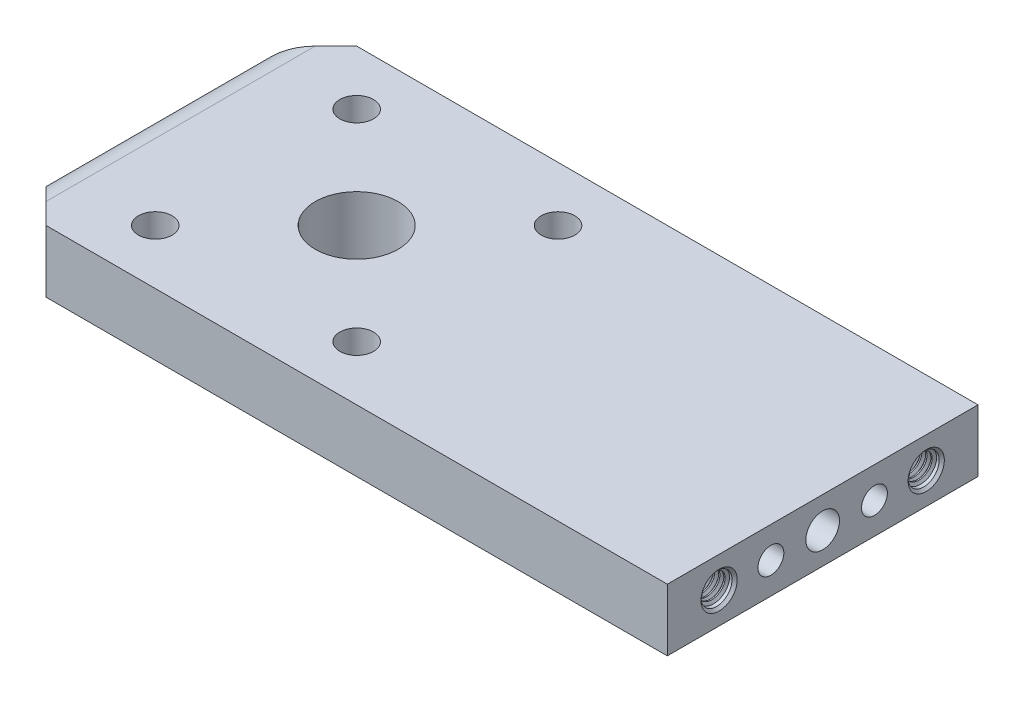
SolidWorks part; units mm, degrees
ref_plane "Front Plane" through (0, 0, 0) normal (0, 0, 1) x (1, 0, 0)
ref_plane "Top Plane" through (0, 0, 0) normal (0, 1, 0) x (1, 0, 0)
ref_plane "Right Plane" through (0, 0, 0) normal (1, 0, 0) x (0, 0, -1)
sketch "Sketch1" plane through (0, 0, 0) normal (0, 1, 0) x (1, 0, 0)
  line L1 (0, 0) -> (-130, 0)
  line L2 (0, 0) -> (0, 60)
  line L3 (0, 60) -> (-130, 60)
  line L4 (-130, 0) -> (-130, 60)
  dimension "D1" = 130
  dimension "D2" = 60
extrude "Boss-Extrude1" add sketch "Sketch1" along normal blind 12
sketch "Sketch2" plane through (0, 12, 0) normal (0, 1, 0) x (1, 0, 0)
  line L0 (-130, 50) -> (-130, 60)
  line L1 (-130, 60) -> (-130, 0) construction
  line L2 (-130, 60) -> (-120, 60)
  line L3 (0, 60) -> (-130, 60) construction
  line L4 (-130, 0) -> (-130, 10)
  line L5 (-130, 0) -> (-120, 0)
  line L6 (-130, 0) -> (0, 0) construction
  line L7 (-130, 50) -> (-120, 60)
  line L8 (-130, 10) -> (-120, 0)
  dimension "D1" = 10
  dimension "D2" = 10
  dimension "D3" = 10
  dimension "D4" = 10
extrude "Cut-Extrude1" cut sketch "Sketch2" against normal through all
sketch "Sketch3" plane through (0, 12, 0) normal (0, 1, 0) x (1, 0, 0)
  line L0 (0, 0) -> (0, 60) construction
  line L1 (-120, 0) -> (0, 0) construction
  circle A0 centre (-90, 30) radius 8
  dimension "D3" = 16
  dimension "D1" = 90
  dimension "D2" = 30
extrude "Cut-Extrude2" cut sketch "Sketch3" against normal through all
sketch "Sketch4" plane through (0, 12, 0) normal (0, 1, 0) x (1, 0, 0)
  circle A1 centre (-109.4474, 10.5565) radius 3.25
  circle A2 centre (-109.4474, 49.4435) radius 3.25
  circle A3 centre (-70.5526, 49.4435) radius 3.25
  circle A4 centre (-70.5526, 10.5565) radius 3.25
  dimension "D3" = 6.5
  dimension "D4" = 6.5
  dimension "D5" = 6.5
  dimension "D6" = 6.5
extrude "Cut-Extrude3" cut sketch "Sketch4" against normal through all
sketch "Sketch6" plane through (0, 0, -60) normal (0, 0, -1) x (-1, 0, 0)
  line L0 (0, 12) -> (120, 12) construction
  circle A0 centre (95, 6) radius 1.5
  circle A1 centre (85, 6) radius 1.5
  dimension "D3" = 3
  dimension "D4" = 3
  dimension "D2" = 6
  dimension "D5" = 10
extrude "Cut-Extrude4" cut sketch "Sketch6" against normal blind 12
sketch "Sketch7" plane through (0, 0, -60) normal (0, 0, -1) x (-1, 0, 0)
  line L0 (0, 0) -> (120, 0) construction
  circle A0 centre (102, 6) radius 3
  circle A1 centre (78, 6) radius 3
  dimension "D2" = 6
  dimension "D4" = 6
  dimension "D1" = 6
  dimension "D5" = 24
extrude "Cut-Extrude5" cut sketch "Sketch7" against normal blind 20
chamfer "Chamfer1" distance 0.5 angle 45 4 edges at (-81, 6, -60) (-86.5, 6, -60) (-96.5, 6, -60) (-105, 6, -60)
thread "Thread4" pitch 1 method extrude profile "Thread Profile4" start angle 0, offset 0, length 15, pitch 1, diameter 6
ref_plane "Plane4" through (-99, 6, -59.5) normal (0, -1, 0) x (1, 0, 0)
sketch "Thread Profile4" plane through (-99, 6, -59.5) normal (0, -1, 0) x (1, 0, 0)
  line L0 (0, 0) -> (0, 1) construction
  line L11 (0, 0) -> (0, 0.875)
  line L12 (0, 0.875) -> (-0.5413, 0.5625)
  line L13 (-0.5413, 0.5625) -> (-0.5413, 0.3125)
  line L15 (-0.5413, 0.3125) -> (0, 0)
  line L17 (-0.5413, 0.4375) -> (0, 0.4375) construction
  point P2 (0, 0)
  dimension "Pitch" = 1
  dimension "Profile_Angle" = 60
  dimension "Profile_Land" = 0.25
  dimension "Profile_Height" = 0.5413
thread "Thread5" pitch 1 method extrude profile "Thread Profile5" start angle 0, offset 0, length 15, pitch 1, diameter 6
ref_plane "Plane5" through (-75, 6, -59.5) normal (0, -1, 0) x (1, 0, 0)
sketch "Thread Profile5" plane through (-75, 6, -59.5) normal (0, -1, 0) x (1, 0, 0)
  line L0 (0, 0) -> (0, 1) construction
  line L11 (0, 0) -> (0, 0.875)
  line L12 (0, 0.875) -> (-0.5413, 0.5625)
  line L13 (-0.5413, 0.5625) -> (-0.5413, 0.3125)
  line L15 (-0.5413, 0.3125) -> (0, 0)
  line L17 (-0.5413, 0.4375) -> (0, 0.4375) construction
  point P2 (0, 0)
  dimension "Pitch" = 1
  dimension "Profile_Angle" = 60
  dimension "Profile_Land" = 0.25
  dimension "Profile_Height" = 0.5413
fillet "Fillet1" radius 6 4 edges at (-130, 6, -10) (-130, 0, -30) (-130, 6, -50) (-130, 12, -30)
sketch "Sketch20" plane through (0, 0, 0) normal (1, 0, 0) x (0, 0, -1)
  line L0 (0, 0) -> (60, 0) construction
  line L1 (60, 12) -> (60, 0) construction
  circle A0 centre (50, 6) radius 3
  circle A1 centre (10, 6) radius 3
  dimension "D3" = 6
  dimension "D4" = 6
  dimension "D1" = 6
  dimension "D2" = 10
  dimension "D5" = 40
extrude "Cut-Extrude6" cut sketch "Sketch20" against normal blind 20
chamfer "Chamfer2" distance 0.5 angle 45 2 edges at (0, 6, -53) (0, 6, -13)
thread "Thread6" pitch 1 method extrude profile "Thread Profile6" start angle 0, offset 0, length 15, pitch 1, diameter 6
ref_plane "Plane6" through (-0.5, 6, -47) normal (0, -1, 0) x (0, 0, 1)
sketch "Thread Profile6" plane through (-0.5, 6, -47) normal (0, -1, 0) x (0, 0, 1)
  line L0 (0, 0) -> (0, 1) construction
  line L11 (0, 0) -> (0, 0.875)
  line L12 (0, 0.875) -> (-0.5413, 0.5625)
  line L13 (-0.5413, 0.5625) -> (-0.5413, 0.3125)
  line L15 (-0.5413, 0.3125) -> (0, 0)
  line L17 (-0.5413, 0.4375) -> (0, 0.4375) construction
  point P2 (0, 0)
  dimension "Pitch" = 1
  dimension "Profile_Angle" = 60
  dimension "Profile_Land" = 0.25
  dimension "Profile_Height" = 0.5413
thread "Thread7" pitch 1 method extrude profile "Thread Profile7" start angle 0, offset 0, length 15, pitch 1, diameter 6
ref_plane "Plane7" through (-0.5, 6, -7) normal (0, -1, 0) x (0, 0, 1)
sketch "Thread Profile7" plane through (-0.5, 6, -7) normal (0, -1, 0) x (0, 0, 1)
  line L0 (0, 0) -> (0, 1) construction
  line L11 (0, 0) -> (0, 0.875)
  line L12 (0, 0.875) -> (-0.5413, 0.5625)
  line L13 (-0.5413, 0.5625) -> (-0.5413, 0.3125)
  line L15 (-0.5413, 0.3125) -> (0, 0)
  line L17 (-0.5413, 0.4375) -> (0, 0.4375) construction
  point P2 (0, 0)
  dimension "Pitch" = 1
  dimension "Profile_Angle" = 60
  dimension "Profile_Land" = 0.25
  dimension "Profile_Height" = 0.5413
sketch "Sketch25" plane through (0, 0, 0) normal (1, 0, 0) x (0, 0, -1)
  line L0 (0, 12) -> (60, 12) construction
  circle A0 centre (40, 6) radius 2.5
  circle A1 centre (50, 6) radius 3.5 construction
  circle A2 centre (20, 6) radius 2.5
  circle A3 centre (10, 6) radius 3.5 construction
  dimension "D2" = 5
  dimension "D4" = 5
  dimension "D1" = 6
  dimension "D3" = 10
  dimension "D5" = 10
extrude "Cut-Extrude7" cut sketch "Sketch25" against normal blind 15.25
sketch "Sketch26" plane through (0, 0, 0) normal (1, 0, 0) x (0, 0, -1)
  line L0 (0, 12) -> (60, 12) construction
  circle A0 centre (30, 6) radius 3.25
  circle A1 centre (20, 6) radius 2.5 construction
  dimension "D2" = 6.5
  dimension "D1" = 6
  dimension "D3" = 10
extrude "Cut-Extrude8" cut sketch "Sketch26" against normal blind 78.5
sketch "Sketch27" plane through (0, 0, 0) normal (0, -1, 0) x (1, 0, 0)
  line L0 (0, 0) -> (0, -60) construction
  line L1 (0, -60) -> (-120, -60) construction
  circle A0 centre (-75, -30) radius 5.5
  dimension "D2" = 11
  dimension "D1" = 75
  dimension "D3" = 30
extrude "Cut-Extrude9" cut sketch "Sketch27" against normal blind 1.5
sketch "Sketch28" plane through (0, 1.5, 0) normal (0, -1, 0) x (1, 0, 0)
  circle A0 centre (-75, -30) radius 3.25
  dimension "D1" = 6.5
extrude "Cut-Extrude10" cut sketch "Sketch28" against normal blind 3.5
